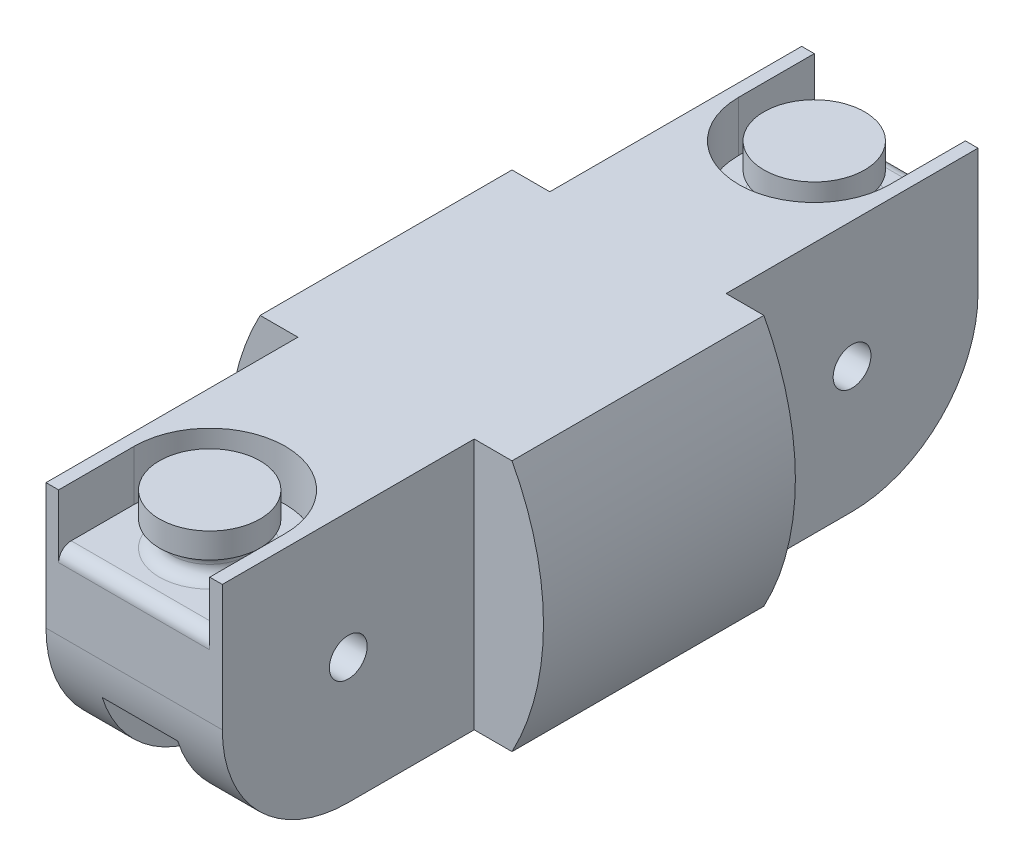
SolidWorks part; units mm, degrees
ref_plane "Alzado" through (0, 0, 0) normal (0, 0, 1) x (1, 0, 0)
ref_plane "Planta" through (0, 0, 0) normal (0, 1, 0) x (1, 0, 0)
ref_plane "Vista lateral" through (0, 0, 0) normal (1, 0, 0) x (0, 0, -1)
sketch "Croquis1" plane through (0, 0, 0) normal (0, 0, 1) x (1, 0, 0)
  line L1 (-10, 10) -> (10, 10)
  line L3 (-10, -10) -> (10, -10)
  line L5 (-10.6997, 8.5598) -> (10.6997, -8.5598) construction
  line L6 (-10.6997, -8.5598) -> (10.6997, 8.5598) construction
  arc A0 (-10, 10) -> (-10, -10) centre (8.75, 0) ccw
  arc A1 (10, -10) -> (10, 10) centre (-8.75, 0) ccw
  point P0 (0, 0)
  point P4 (12.5, 0)
  point P13 (-12.5, 0)
  dimension "D1" = 20
  dimension "D2" = 25
  dimension "D3" = 20
extrude "Saliente-Extruir1" add sketch "Croquis1" along normal blind 20
sketch "Croquis5" plane through (0, 0, 0) normal (0, 0, -1) x (-1, 0, 0)
  line L0 (10, -10) -> (-10, -10) construction
  circle A0 centre (0, -7) radius 1.5
  dimension "D2" = 3
  dimension "D1" = 3
extrude "Cortar-Extruir3" cut sketch "Croquis5" against normal blind 20
sketch "Croquis2" plane through (0, 0, 0) normal (0, 0, -1) x (-1, 0, 0)
  line L0 (10, -10) -> (-10, -10) construction
  line L2 (-7, 10) -> (-7, -10)
  line L3 (-7, -10) -> (-3, -10)
  line L4 (7, 10) -> (7, -10)
  line L5 (-7, 10) -> (7, -10) construction
  line L6 (-7, -10) -> (7, 10) construction
  line L8 (3, -3) -> (3, -10)
  line L10 (3, -10) -> (7, -10)
  line L11 (-3, -3) -> (3, -3)
  line L12 (-7, 10) -> (7, 10)
  line L13 (-3, -3) -> (-3, -10)
  point P0 (0, 0)
  dimension "D1" = 14
  dimension "D3" = 4
  dimension "D4" = 7
extrude "Saliente-Extruir2" add sketch "Croquis2" along normal blind 20
sketch "Croquis3" plane through (0, 0, 20) normal (0, 0, 1) x (1, 0, 0)
  line L0 (-10, -10) -> (10, -10) construction
  line L2 (-7, 10) -> (-7, -10)
  line L3 (-7, -10) -> (-3, -10)
  line L4 (7, 10) -> (7, -10)
  line L5 (-7, 10) -> (7, -10) construction
  line L6 (-7, -10) -> (7, 10) construction
  line L8 (3, -3) -> (3, -10)
  line L9 (3, -10) -> (7, -10)
  line L11 (-3, -3) -> (3, -3)
  line L12 (-3, -3) -> (-3, -10)
  line L13 (-7, 10) -> (7, 10)
  point P0 (0, 0)
  dimension "D1" = 14
  dimension "D3" = 4
  dimension "D4" = 7
extrude "Saliente-Extruir3" add sketch "Croquis3" along normal blind 20
sketch "Croquis4" plane through (-7, 0, 0) normal (-1, 0, 0) x (0, 0, 1)
  line L1 (-20, -10) -> (-20, 10) construction
  line L3 (40, 10) -> (40, -10) construction
  line L4 (-20, -10) -> (0, -10) construction
  line L5 (40, -10) -> (20, -10) construction
  circle A0 centre (-10, 0) radius 1.5
  circle A1 centre (30, 0) radius 1.5
  dimension "D3" = 3
  dimension "D6" = 3
  dimension "D1" = 10
  dimension "D2" = 10
  dimension "D4" = 10
  dimension "D5" = 10
extrude "Cortar-Extruir2" cut sketch "Croquis4" against normal blind 14
fillet "Redondeo1" radius 10 4 edges at (5, -10, 40) (-5, -10, 40) (5, -10, -20) (-5, -10, -20)
sketch "Sketch1" plane through (0, 10, 0) normal (0, 1, 0) x (1, 0, 0)
  line L0 (-7, 20) -> (7, 20) construction
  line L1 (7, -40) -> (-7, -40) construction
  line L4 (-6, 14) -> (-6, 20)
  line L5 (-6, 20) -> (6, 20)
  line L6 (6, 14) -> (6, 20)
  line L8 (-6, -34) -> (-6, -40)
  line L9 (-6, -40) -> (6, -40)
  line L10 (6, -34) -> (6, -40)
  arc A0 (-6, 14) -> (6, 14) centre (0, 14) ccw
  arc A1 (6, -34) -> (-6, -34) centre (0, -34) ccw
  dimension "D1" = 12
  dimension "D3" = 12
  dimension "D2" = 6
  dimension "D4" = 6
extrude "Cut-Extrude1" cut sketch "Sketch1" against normal blind 4
sketch "Sketch2" plane through (0, 6, 0) normal (0, 1, 0) x (1, 0, 0)
  circle A0 centre (0, -34) radius 3
  circle A1 centre (0, 14) radius 3
  dimension "D1" = 6
  dimension "D2" = 6
extrude "Boss-Extrude1" add sketch "Sketch2" along normal blind 2
sketch "Sketch3" plane through (0, 8, 0) normal (0, 1, 0) x (1, 0, 0)
  circle A0 centre (0, -34) radius 4
  circle A1 centre (0, 14) radius 4
  dimension "D1" = 8
  dimension "D2" = 8
extrude "Boss-Extrude2" add sketch "Sketch3" along normal blind 2
fillet "Fillet1" radius 1 4 edges at (0, 8, 37) (0, 6, 37) (0, 8, -11) (0, 6, -11)
fillet "Fillet2" radius 1 2 edges at (0, 6, 40) (0, 6, -20)
fillet "Fillet3" radius 1 2 edges at (-1.5, -7, 20) (-1.5, -7, 0)
